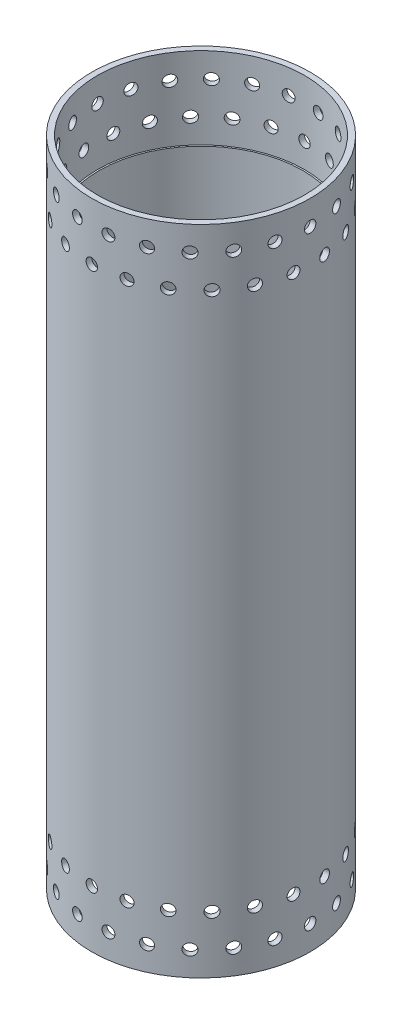
SolidWorks part; units mm, degrees
material "3.1325 (EN-AW 2017A)"
ref_plane "Front Plane" through (0, 0, 0) normal (0, 0, 1) x (1, 0, 0)
ref_plane "Top Plane" through (0, 0, 0) normal (0, 1, 0) x (1, 0, 0)
ref_plane "Right Plane" through (0, 0, 0) normal (1, 0, 0) x (0, 0, -1)
sketch "Sketch1" plane through (0, 0, 0) normal (0, 1, 0) x (1, 0, 0)
  circle A0 centre (0, 0) radius 67
  circle A1 centre (0, 0) radius 62.5
  dimension "D1" = 134
  dimension "D2" = 125
extrude "Boss-Extrude1" add sketch "Sketch1" along normal blind 400
sketch "Sketch2" plane through (0, 400, 0) normal (0, 1, 0) x (1, 0, 0)
  circle A0 centre (0, 0) radius 62.5 construction
  circle A1 centre (0, 0) radius 62.5
  circle A2 centre (0, 0) radius 63.5
  dimension "D1" = 1
extrude "Cut-Extrude1" cut sketch "Sketch2" against normal blind 50
ref_plane "Plane1" through (-67, 0, 0) normal (-1, 0, 0) x (0, 0, 1)
hole_wizard "Ø7.0 (7) Diameter Hole1" positions "Sketch3" profile "Sketch4" hole size "Ø7.0" standard "ANSI Metric" end condition up to next
sketch "Sketch3" plane through (-67, 0, 0) normal (-1, 0, 0) x (0, 0, 1)
  line L0 (67, 400) -> (-67, 400) construction
  point P0 (0, 385)
  dimension "D1" = 15
sketch "Sketch4" plane through (-67, 385, 0) normal (0, 1, 0) x (0, 0, 1)
  line L0 (0, 0) -> (0, 3.5)
  line L1 (0, 3.5) -> (3.5, 3.5)
  line L2 (3.5, 3.5) -> (3.5, 0)
  line L5 (3.5, 0) -> (0, 0)
  line L11 (0, -6.35) -> (0, 107.95) construction
  dimension "Thru Hole Dia." = 7
  dimension "Thru Hole Depth" = 3.5
pattern_circular "CirPattern1" count 22 over 360 about axis through (0, 400, 0) along (0, -1, 0) of "Ø7.0 (7) Diameter Hole1"
ref_plane "Plane2" through (66.318, 0, 9.5351) normal (0.9898, 0, 0.1423) x (0, -1, 0)
hole_wizard "Ø7.0 (7) Diameter Hole2" positions "Sketch5" profile "Sketch6" hole size "Ø7.0" standard "ANSI Metric" end condition up to next
sketch "Sketch5" plane through (66.318, 0, 9.5351) normal (0.9898, 0, 0.1423) x (0, -1, 0)
  line L0 (-400, 67) -> (-400, -67) construction
  point P1 (-365, 0)
  dimension "D1" = 35
sketch "Sketch6" plane through (66.318, 365, 9.5351) normal (0, 1, 0) x (0.1423, 0, -0.9898)
  line L0 (0, 0) -> (0, 3.5)
  line L1 (0, 3.5) -> (3.5, 3.5)
  line L2 (3.5, 3.5) -> (3.5, 0)
  line L5 (3.5, 0) -> (0, 0)
  line L11 (0, -6.35) -> (0, 107.95) construction
  dimension "Thru Hole Dia." = 7
  dimension "Thru Hole Depth" = 3.5
pattern_circular "CirPattern2" count 22 over 360 about axis through (0, 400, 0) along (0, -1, 0) of "Ø7.0 (7) Diameter Hole2"
ref_plane "Plane3" through (0, 200, 0) normal (0, 1, 0) x (1, 0, 0)
mirror "Mirror1" about plane through (0, 200, 0) normal (0, 1, 0) of "CirPattern2", "CirPattern1", "Cut-Extrude1"
